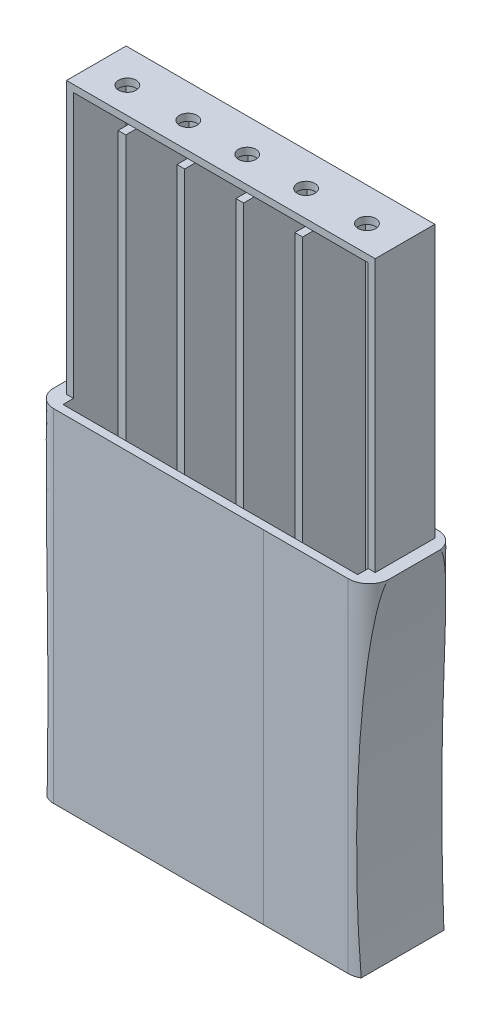
SolidWorks part; units mm, degrees
ref_plane "Front Plane" through (0, 0, 0) normal (0, 0, 1) x (1, 0, 0)
ref_plane "Top Plane" through (0, 0, 0) normal (0, 1, 0) x (1, 0, 0)
ref_plane "Right Plane" through (0, 0, 0) normal (1, 0, 0) x (0, 0, -1)
ref_plane "Plane1" through (0, 10, 0) normal (0, 1, 0) x (1, 0, 0)
sketch "Sketch1" plane through (0, 0, 0) normal (0, 0, 1) x (1, 0, 0)
  line L1 (-44, -87.5) -> (44, -87.5)
  line L2 (-44, -87.5) -> (-44, 87.5)
  line L3 (-44, 87.5) -> (44, 87.5)
  line L4 (44, -87.5) -> (44, 87.5)
  line L5 (-44, -87.5) -> (44, 87.5) construction
  line L6 (-44, 87.5) -> (44, -87.5) construction
  point P0 (0, 0)
  dimension "D1" = 88
  dimension "D2" = 175
extrude "Boss-Extrude1" add sketch "Sketch1" along normal blind 2
sketch "Sketch2" plane through (0, 0, 2) normal (0, 0, 1) x (1, 0, 0)
  line L4 (44, -87.5) -> (44, 87.5)
  line L5 (44, 87.5) -> (-44, 87.5)
  line L6 (-44, 87.5) -> (-44, -87.5)
  line L7 (-44, -87.5) -> (44, -87.5)
  line L8 (44, -87.5) -> (44, 87.5)
  line L9 (44, 87.5) -> (-44, 87.5)
  line L10 (-44, 87.5) -> (-44, -87.5)
  line L11 (-44, -87.5) -> (44, -87.5)
  dimension "D1" = 0
extrude "Extrude-Thin1" add sketch "Sketch2" along normal blind 15 thin thin type one direction reverse wall 2
sketch "Sketch7" plane through (0, 10, 0) normal (0, -1, 0) x (1, 0, 0)
  line L10 (-42.3768, -2.407) -> (42.5401, -2.407)
  line L11 (47.6224, 2.5172) -> (47.6224, 16.4468)
  line L12 (41.5429, 22.3538) -> (17.5198, 22.3437)
  line L13 (17.5198, 22.3437) -> (-42.3262, 22.3337)
  line L14 (-47.3776, 17.3465) -> (-47.3776, 2.5515)
  spline S8 degree 3 poles (42.5401, -2.407) (42.8706, -2.4078) (43.196, -2.3778) (43.8369, -2.2583) (44.1553, -2.1674) (44.7669, -1.9274) (45.0576, -1.7798) (45.6085, -1.4299) (45.8711, -1.2247) (46.3442, -0.773) (46.5566, -0.526) (46.8382, -0.1231) (46.9263, 0.0175) (47.0866, 0.3047) (47.159, 0.4514) (47.3532, 0.9003) (47.4524, 1.2115) (47.5875, 1.8587) (47.6216, 2.1864) (47.6224, 2.5172) knots 0 0 0 0 0.125 0.125 0.25 0.25 0.375 0.375 0.5 0.5 0.625 0.625 0.6875 0.6875 0.75 0.75 0.875 0.875 1 1 1 1
  spline S9 degree 3 poles (47.6224, 16.4468) (47.6224, 16.843) (47.5828, 17.2324) (47.4656, 17.8067) (47.4168, 17.9965) (47.2994, 18.3728) (47.2305, 18.5591) (46.9987, 19.1005) (46.8095, 19.4421) (46.474, 19.926) (46.3528, 20.0833) (46.0967, 20.383) (45.962, 20.5254) (45.5387, 20.9312) (45.2308, 21.1731) (44.563, 21.5988) (44.2136, 21.7758) (43.4861, 22.0621) (43.1044, 22.1719) (42.3303, 22.3175) (41.9388, 22.3539) (41.5429, 22.3538) knots 0 0 0 0 0.125 0.125 0.1875 0.1875 0.25 0.25 0.375 0.375 0.4375 0.4375 0.5 0.5 0.625 0.625 0.75 0.75 0.875 0.875 1 1 1 1
  spline S10 degree 3 poles (-42.3262, 22.3337) (-42.6576, 22.3345) (-42.9836, 22.3031) (-43.4649, 22.2099) (-43.624, 22.171) (-43.9396, 22.0774) (-44.0966, 22.0224) (-44.5538, 21.8366) (-44.8431, 21.6848) (-45.3911, 21.3255) (-45.6513, 21.1158) (-46.1184, 20.6569) (-46.3281, 20.4063) (-46.6064, 19.998) (-46.6931, 19.856) (-46.8504, 19.5673) (-46.9214, 19.4199) (-47.1124, 18.9685) (-47.2104, 18.6543) (-47.3432, 18.0058) (-47.3769, 17.678) (-47.3776, 17.3465) knots 0 0 0 0 0.125 0.125 0.1875 0.1875 0.25 0.25 0.375 0.375 0.5 0.5 0.625 0.625 0.6875 0.6875 0.75 0.75 0.875 0.875 1 1 1 1
  spline S11 degree 3 poles (-47.3776, 2.5515) (-47.3776, 2.223) (-47.3453, 1.9) (-47.25, 1.4233) (-47.2104, 1.2658) (-47.1151, 0.9534) (-47.0592, 0.7983) (-46.8708, 0.3471) (-46.717, 0.0618) (-46.3535, -0.4777) (-46.142, -0.7328) (-45.6803, -1.1896) (-45.4283, -1.3943) (-44.8814, -1.7557) (-44.5911, -1.9086) (-43.9903, -2.1544) (-43.6758, -2.2489) (-43.0316, -2.3754) (-42.706, -2.407) (-42.3768, -2.407) knots 0 0 0 0 0.125 0.125 0.1875 0.1875 0.25 0.25 0.375 0.375 0.5 0.5 0.625 0.625 0.75 0.75 0.875 0.875 1 1 1 1
extrude "Boss-Extrude2" add sketch "Sketch7" along normal up to surface (97.5 mm away) up to face at (0, -87.5, 8.5)
sketch "Sketch10" plane through (0, 0, 2) normal (0, 0, -1) x (-1, 0, 0)
  line L8 (42, -85.5) -> (42, 85.5)
  line L9 (-42, -85.5) -> (42, -85.5)
  line L10 (-42, 85.5) -> (-42, -85.5)
  line L11 (42, 85.5) -> (-42, 85.5)
extrude "Cut-Extrude2" cut sketch "Sketch10" against normal blind 18
sketch "Sketch3" plane through (0, 0, 2) normal (0, 0, 1) x (1, 0, 0)
  line L0 (-25.2, 85.5) -> (-25.2, -85.5)
  line L1 (42, 85.5) -> (-42, 85.5) construction
  line L3 (-8.4, 85.5) -> (-8.4, -85.5)
  line L4 (42, 85.5) -> (-42, 85.5) construction
  line L5 (25.2, 85.5) -> (25.2, -85.5)
  line L6 (8.4, 85.5) -> (8.4, -85.5)
  line L8 (-42, 85.5) -> (-42, -85.5) construction
  line L9 (42, -85.5) -> (42, 85.5) construction
  line L11 (42, -85.5) -> (-42, -85.5) construction
  dimension "D1" = 16.8
  dimension "D2" = 16.8
  dimension "D3" = 16.8
  dimension "D4" = 16.8
  dimension "D5" = 16.8
extrude "Extrude-Thin2" add sketch "Sketch3" along normal blind 18 thin thin type mid plane wall 2.2
sketch "Sketch4" plane through (0, 87.5, 0) normal (0, 1, 0) x (1, 0, 0)
  line L0 (26.3, -17) -> (26.3, -2) construction
  line L1 (26.3, -2) -> (42, -2) construction
  line L2 (42, -2) -> (42, -17) construction
  line L3 (42, -17) -> (26.3, -17) construction
  line L4 (9.5, -17) -> (9.5, -2) construction
  line L5 (9.5, -2) -> (24.1, -2) construction
  line L6 (24.1, -2) -> (24.1, -17) construction
  line L7 (24.1, -17) -> (9.5, -17) construction
  line L8 (-7.3, -2) -> (7.3, -2) construction
  line L9 (7.3, -2) -> (7.3, -17) construction
  line L10 (7.3, -17) -> (-7.3, -17) construction
  line L11 (-7.3, -17) -> (-7.3, -2) construction
  line L12 (-24.1, -2) -> (-9.5, -2) construction
  line L13 (-9.5, -2) -> (-9.5, -17) construction
  line L14 (-9.5, -17) -> (-24.1, -17) construction
  line L15 (-24.1, -17) -> (-24.1, -2) construction
  line L16 (-42, -2) -> (-26.3, -2) construction
  line L17 (-26.3, -2) -> (-26.3, -17) construction
  line L18 (-26.3, -17) -> (-42, -17) construction
  line L19 (-42, -17) -> (-42, -2) construction
  line L20 (26.3, -17) -> (26.3, -2) construction
  line L21 (26.3, -2) -> (42, -2) construction
  line L22 (42, -2) -> (42, -17) construction
  line L23 (42, -17) -> (26.3, -17) construction
  line L24 (9.5, -17) -> (9.5, -2) construction
  line L25 (9.5, -2) -> (24.1, -2) construction
  line L26 (24.1, -2) -> (24.1, -17) construction
  line L27 (24.1, -17) -> (9.5, -17) construction
  line L28 (-7.3, -2) -> (7.3, -2) construction
  line L29 (7.3, -2) -> (7.3, -17) construction
  line L30 (7.3, -17) -> (-7.3, -17) construction
  line L31 (-7.3, -17) -> (-7.3, -2) construction
  line L32 (-24.1, -2) -> (-9.5, -2) construction
  line L33 (-9.5, -2) -> (-9.5, -17) construction
  line L34 (-9.5, -17) -> (-24.1, -17) construction
  line L35 (-24.1, -17) -> (-24.1, -2) construction
  line L36 (-42, -2) -> (-26.3, -2) construction
  line L37 (-26.3, -2) -> (-26.3, -17) construction
  line L38 (-26.3, -17) -> (-42, -17) construction
  line L39 (-42, -17) -> (-42, -2) construction
  line L40 (42, -9.5) -> (-42, -9.5) construction
  line L41 (-16.8, -17) -> (-16.8, -2) construction
  line L42 (-34.15, -17) -> (-34.15, -2) construction
  line L43 (0, -17) -> (0, -2) construction
  line L44 (16.8, -17) -> (16.8, -2) construction
  line L45 (34.15, -17) -> (34.15, -2) construction
  point P26 (34.15, -9.5)
  point P28 (16.8, -9.5)
  point P30 (0, -9.5)
  point P31 (-16.8, -9.5)
  point P34 (-34.15, -9.5)
hole_wizard "Ø5.0mm Dowel Hole3" positions "Sketch5" profile "Sketch6" hole size "Ø5.0" standard "BSI" end condition up to next
sketch "Sketch5" plane through (0, 87.5, 0) normal (0, 1, 0) x (1, 0, 0)
  line L0 (-34.15, -17) -> (-34.15, -2) construction
  line L1 (-16.8, -17) -> (-16.8, -2) construction
  point P0 (-34.15, -9.5)
  point P4 (-16.8, -9.5)
  point P8 (0, -9.5)
  point P11 (16.8, -9.5)
  point P14 (34.15, -9.5)
sketch "Sketch6" plane through (-34.15, 87.5, 9.5) normal (1, 0, 0) x (0, 0, 1)
  line L0 (0, 0) -> (0, 2)
  line L1 (0, 2) -> (2.5, 2)
  line L2 (2.5, 2) -> (2.5, 0)
  line L5 (2.5, 0) -> (0, 0)
  line L11 (0, -6.35) -> (0, 107.95) construction
  dimension "Thru Hole Dia." = 5
  dimension "Thru Hole Depth" = 2
sketch "Sketch11" plane through (0, 0, 0) normal (0, 0, 1) x (1, 0, 0)
  line L0 (-47.3776, -87.5) -> (-47.3776, 10) construction
  line L1 (47.6224, -87.5) -> (47.6224, 10) construction
  line L2 (-47.3776, -87.5) -> (-47.3776, 10) construction
  line L3 (47.6224, -87.5) -> (47.6224, 10) construction
  line L6 (-42.3262, -87.5) -> (-42.3262, 10) construction
  line L7 (41.5429, -87.5) -> (41.5429, 10) construction
  line L8 (-47.3776, 10) -> (-88.5977, 10)
  line L9 (13.6518, 10) -> (-13.6518, 10) construction
  line L10 (-88.5977, 10) -> (-88.5977, -88.3549)
  line L11 (-88.5977, -88.3549) -> (-44.8519, -87.5)
  line L12 (47.6224, 10) -> (76.6267, 12.525)
  line L13 (76.6267, 12.525) -> (69.1799, -99.2923)
  line L14 (69.1799, -99.2923) -> (44.5826, -87.5)
  line L15 (-47.3776, -87.5) -> (-42.3262, -87.5) construction
  line L16 (41.5429, -87.5) -> (47.6224, -87.5) construction
  spline S0 degree 2 poles (-47.3776, 10) (-43.3223, -38.6841) (-44.8519, -87.5) knots 0 0 0 1 1 1
  spline S1 degree 2 poles (47.6224, 10) (41.8008, -38.6312) (44.5826, -87.5) knots 0 0 0 1 1 1
  dimension "D1" = 2.3
  dimension "D2" = 2.3
extrude "Cut-Extrude3" cut sketch "Sketch11" against normal through all both and the other way through all
